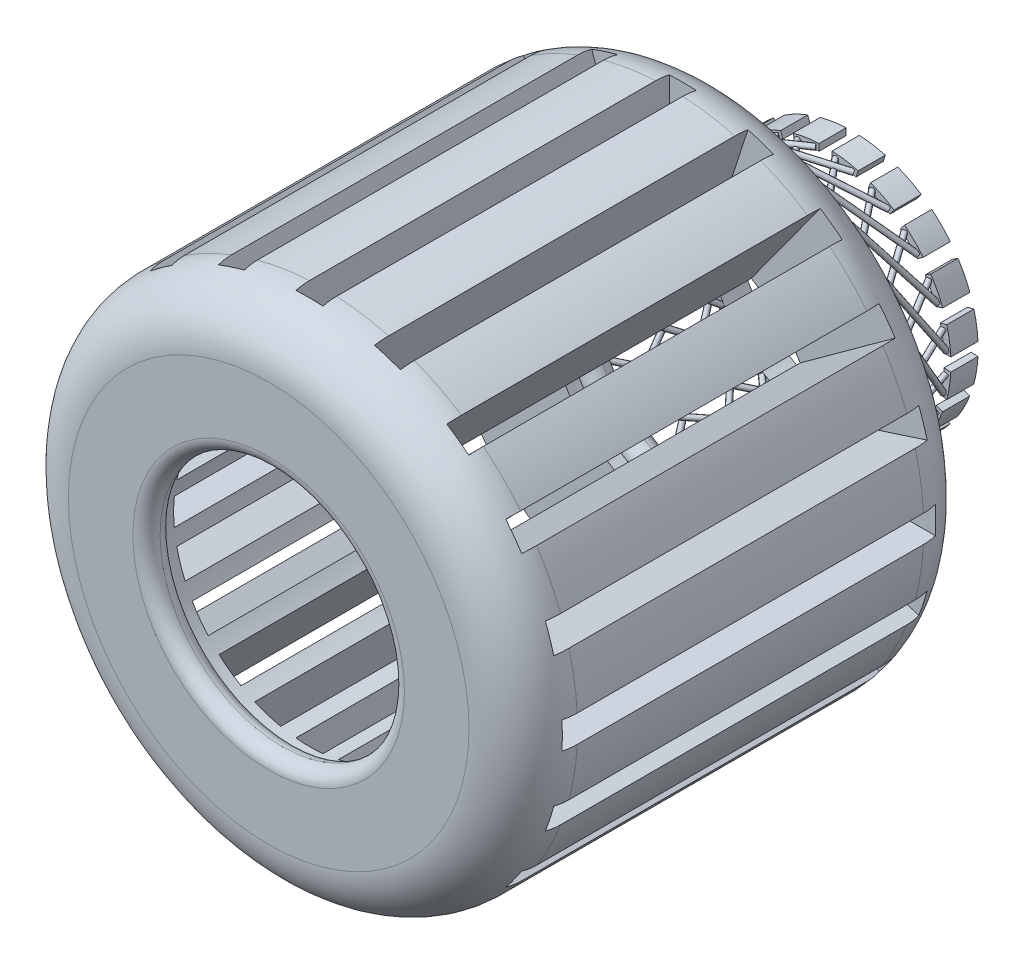
SolidWorks part; units mm, degrees
ref_plane "Plan de face" through (0, 0, 0) normal (0, 0, 1) x (1, 0, 0)
ref_plane "Plan de dessus" through (0, 0, 0) normal (0, 1, 0) x (1, 0, 0)
ref_plane "Plan de droite" through (0, 0, 0) normal (1, 0, 0) x (0, 0, -1)
sketch "Esquisse2" plane through (0, 0, 0) normal (0, 0, 1) x (1, 0, 0)
  line L0 (0, 0) -> (0, 47.4656) construction
  circle A0 centre (0, 0) radius 20
  circle A1 centre (0, 0) radius 37.5
  dimension "D1" = 40
  dimension "D2" = 75
extrude "Extrusion1" add sketch "Esquisse2" along normal blind 2
sketch "Esquisse4" plane through (0, 0, 0) normal (0, 0, -1) x (-1, 0, 0)
  line L0 (0, 0) -> (0, 38.7236) construction
  line L1 (2, 37.4466) -> (2, 19.8997)
  line L3 (0, 0) -> (13.4385, 41.3593) construction
  line L4 (9.6695, 36.2319) -> (4.2472, 19.5438)
  circle A0 centre (0, 0) radius 37.5 construction
  circle A1 centre (0, 0) radius 20 construction
  arc A2 (9.6695, 36.2319) -> (2, 37.4466) centre (0, 0) ccw
  arc A3 (4.2472, 19.5438) -> (2, 19.8997) centre (0, 0) ccw
  dimension "D1" = 4
  dimension "D2" = 18
  dimension "D3" = 4
extrude "Extrusion2" add sketch "Esquisse4" along normal blind 55
ref_axis "Axe1" through (0, 0, 2) along (0, 0, -1)
pattern_circular "Répétition circulaire1" count 20 over 360 about axis through (0, 0, 2) along (0, 0, -1) of "Extrusion2"
sketch "Esquisse5" plane through (0, 0, -55) normal (0, 0, -1) x (-1, 0, 0)
  circle A0 centre (0, 0) radius 37.5
  circle A1 centre (0, 0) radius 20
extrude "Extrusion3" add sketch "Esquisse5" along normal blind 2
sketch "Esquisse7" plane through (0, 0, -57) normal (0, 0, -1) x (-1, 0, 0)
  circle A0 centre (0, 0) radius 37.5
  circle A1 centre (0, 0) radius 18
  dimension "D1" = 75
  dimension "D2" = 36
extrude "Extrusion4" add sketch "Esquisse7" along normal blind 4
sketch "Esquisse8" plane through (0, 0, 2) normal (0, 0, 1) x (1, 0, 0)
  circle A0 centre (0, 0) radius 37.5
  circle A1 centre (0, 0) radius 18
  dimension "D1" = 75
  dimension "D2" = 36
extrude "Extrusion5" add sketch "Esquisse8" along normal blind 4
fillet "Congé1" radius 8 2 edges at (-37.5, 0, -61) (37.5, 0, 6)
fillet "Congé2" radius 2 4 edges at (-18, 0, -57) (-18, 0, -61) (18, 0, 6) (18, 0, 2)
ref_plane "Plan4" through (0, 0, -76) normal (0, 0, -1) x (-1, 0, 0)
sketch "Esquisse9" plane through (0, 0, -76) normal (0, 0, -1) x (-1, 0, 0)
  circle A0 centre (0, 0) radius 17.875
  point P3 (1.3894, 17.8209)
  point P4 (4.1102, 17.396)
  dimension "D1" = 35.75
sketch "Esquisse10" plane through (0, 0, -61) normal (0, 0, -1) x (-1, 0, 0)
  circle A0 centre (0, 0) radius 29.5 construction
  circle A1 centre (0, 0) radius 20 construction
  point P0 (23.5088, 17.8209)
  point P1 (-8.295, 18.1987)
sketch3d "Esquisse3D1"
  line L0 (-1.3894, 17.8209, -76) -> (-23.5088, 17.8209, -61)
ref_plane "Plan5" through (-1.3894, 17.8209, -76) normal (-0.8276, 0, 0.5613) x (0.5613, 0, 0.8276)
sketch "Esquisse11" plane through (-1.3894, 17.8209, -76) normal (-0.8276, 0, 0.5613) x (0.5613, 0, 0.8276)
  circle A0 centre (0, 0) radius 0.375
  dimension "D1" = 0.75
sweep "Balayage1" add profiles "Esquisse11" path "Esquisse3D1"
pattern_circular "Répétition circulaire2" count 20 over 360 about axis through (0, 0, 2) along (0, 0, -1) of "Balayage1"
sketch3d "Esquisse3D2"
  line L0 (-4.1102, 17.396, -76) -> (8.295, 18.1987, -61)
ref_plane "Plan6" through (-4.1102, 17.396, -76) normal (0.6368, 0.0412, 0.77) x (0.7711, -0.0354, -0.6358)
sketch "Esquisse12" plane through (-4.1102, 17.396, -76) normal (0.6368, 0.0412, 0.77) x (0.7711, -0.0354, -0.6358)
  circle A0 centre (0, 0) radius 0.375
  dimension "D1" = 0.75
sweep "Balayage2" add profiles "Esquisse12" path "Esquisse3D2"
pattern_circular "Répétition circulaire3" count 20 over 360 about axis through (0, 0, 2) along (0, 0, -1) of "Balayage2"
sketch "Esquisse13" plane through (0, 0, -76) normal (0, 0, -1) x (-1, 0, 0)
  line L0 (0.9302, 17.4753) -> (0.9302, 18.4766)
  line L1 (4.504, 16.9105) -> (4.7614, 17.8768)
  arc A0 (4.504, 16.9105) -> (0.9302, 17.4753) centre (0, 0) ccw
  arc A1 (4.7614, 17.8768) -> (0.9302, 18.4766) centre (0, 0) ccw
  dimension "D1" = 35
  dimension "D2" = 37
extrude "Extrusion6" add sketch "Esquisse13" along normal blind 4
pattern_circular "Répétition circulaire4" count 20 over 360 about axis through (0, 0, 2) along (0, 0, -1) of "Extrusion6"
